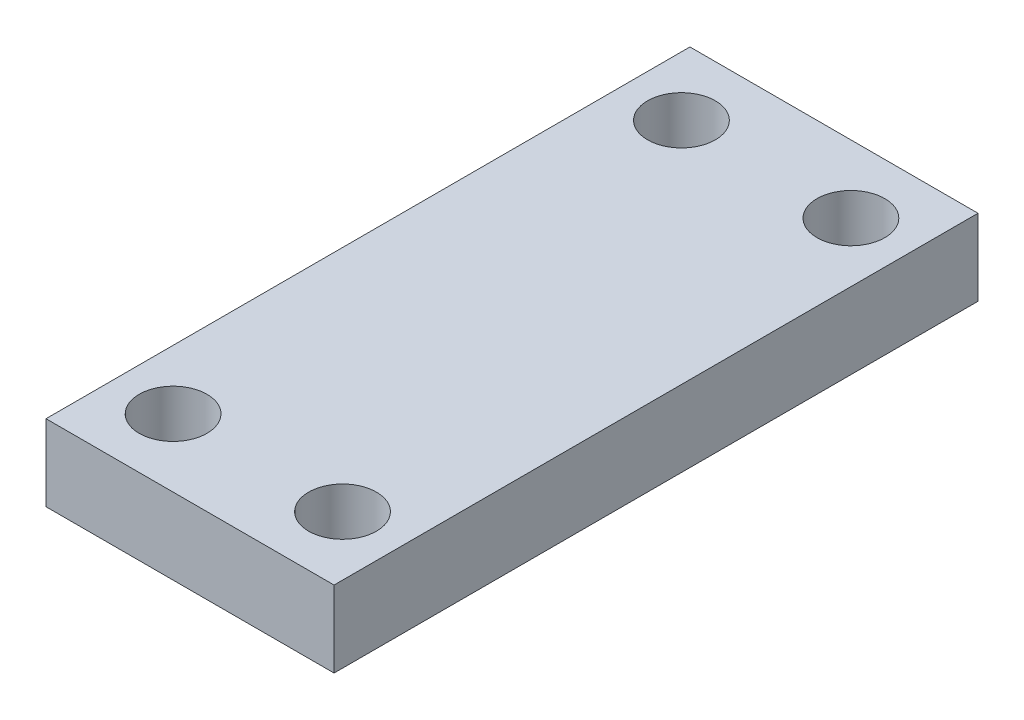
SolidWorks part; units mm, degrees
ref_plane "Front Plane" through (0, 0, 0) normal (0, 0, 1) x (1, 0, 0)
ref_plane "Top Plane" through (0, 0, 0) normal (0, 1, 0) x (1, 0, 0)
ref_plane "Right Plane" through (0, 0, 0) normal (1, 0, 0) x (0, 0, -1)
sketch "Sketch1" plane through (0, 0, 0) normal (0, 1, 0) x (1, 0, 0)
  line L1 (-8.5, -19) -> (8.5, -19)
  line L2 (-8.5, -19) -> (-8.5, 19)
  line L3 (-8.5, 19) -> (8.5, 19)
  line L4 (8.5, -19) -> (8.5, 19)
  line L5 (-8.5, -19) -> (8.5, 19) construction
  line L6 (-8.5, 19) -> (8.5, -19) construction
  line L7 (-5, -15) -> (5, -15) construction
  line L8 (-5, -15) -> (-5, 15) construction
  line L9 (-5, 15) -> (5, 15) construction
  line L10 (5, -15) -> (5, 15) construction
  line L11 (-5, -15) -> (5, 15) construction
  line L12 (-5, 15) -> (5, -15) construction
  circle A0 centre (-5, 15) radius 2
  circle A1 centre (5, 15) radius 2
  circle A2 centre (5, -15) radius 2
  circle A3 centre (-5, -15) radius 2
  point P0 (0, 0)
  point P6 (0, 0)
  dimension "D1" = 4
  dimension "D2" = 17
  dimension "D3" = 38
  dimension "D4" = 30
  dimension "D5" = 10
extrude "Boss-Extrude1" add sketch "Sketch1" along normal blind 4.5 contours L3 L4 L1 L2
extrude "Cut-Extrude1" cut sketch "Sketch1<3>" along normal blind 4.5 contours A0 | A1 | A2 | A3
sketch "Sketch1<3>" plane through (0, 0, 0) normal (0, 1, 0) x (1, 0, 0) same geometry as "Sketch1"
